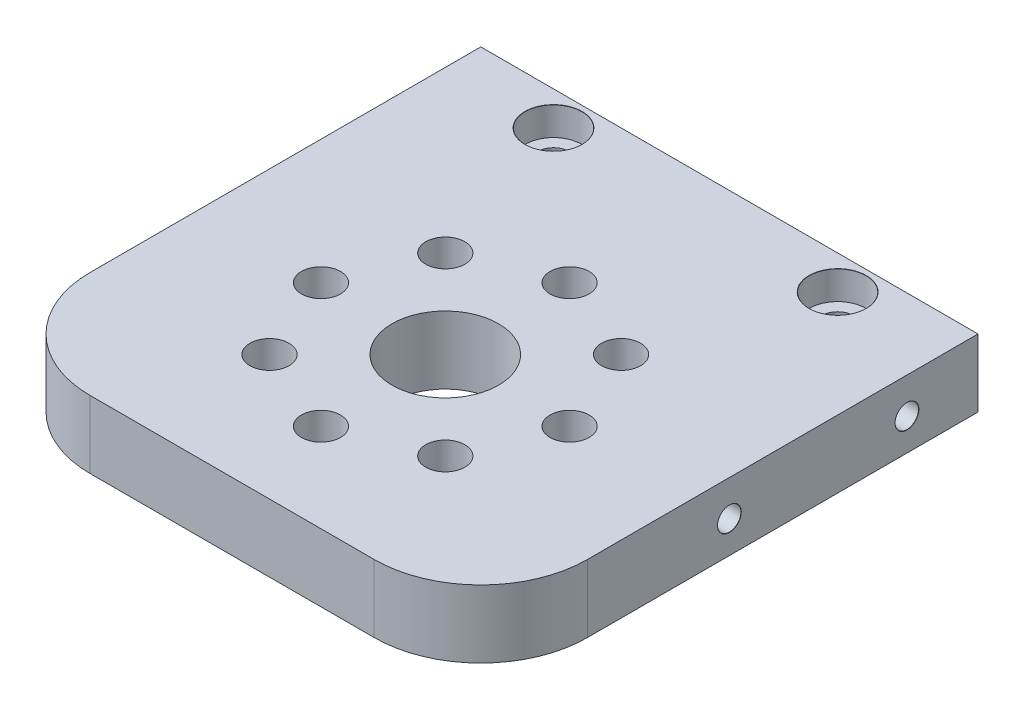
SolidWorks part; units mm, degrees
material "1060 Alloy"
ref_plane "Front Plane" through (0, 0, 0) normal (0, 0, 1) x (1, 0, 0)
ref_plane "Top Plane" through (0, 0, 0) normal (0, 1, 0) x (1, 0, 0)
ref_plane "Right Plane" through (0, 0, 0) normal (1, 0, 0) x (0, 0, -1)
sketch "Sketch1" plane through (0, 0, 0) normal (0, 1, 0) x (1, 0, 0)
  line L1 (-35, -35) -> (35, -35)
  line L2 (-35, -35) -> (-35, 35)
  line L3 (-35, 35) -> (35, 35)
  line L4 (35, -35) -> (35, 35)
  line L5 (-35, -35) -> (35, 35) construction
  line L6 (-35, 35) -> (35, -35) construction
  point P0 (0, 0)
  dimension "D1" = 70
  dimension "D2" = 70
extrude "Boss-Extrude1" add sketch "Sketch1" along normal blind 9.525
sketch "Sketch2" plane through (0, 0, 0) normal (0, -1, 0) x (1, 0, 0)
  line L1 (-35, 35) -> (35, 35) construction
  line L2 (-35, -35) -> (-35, 35) construction
  circle A0 centre (0, 5) radius 17.5 construction
  point P4 (0, 22.5)
  point P6 (12.3744, 17.3744)
  point P7 (17.5, 5)
  point P8 (12.3744, -7.3744)
  point P9 (0, -12.5)
  point P10 (-12.3744, -7.3744)
  point P11 (-17.5, 5)
  point P12 (-12.3744, 17.3744)
  point P13 (0, 5)
  dimension "D2" = 35
  dimension "D3" = 30
  dimension "D4" = 35
  dimension "D1" = 8
hole_wizard "CBORE for M5 SHCS2" positions "Sketch3" profile "Sketch4" counterbore size "M5" standard "ANSI Metric" end condition through all
sketch "Sketch3" plane through (0, 0, 0) normal (0, -1, 0) x (-1, 0, 0)
  point P0 (0, -22.5)
  point P3 (-12.3744, -17.3744)
  point P6 (-17.5, -5)
  point P9 (-12.3744, 7.3744)
  point P12 (0, 12.5)
  point P15 (12.3744, 7.3744)
  point P18 (17.5, -5)
  point P21 (12.3744, -17.3744)
sketch "Sketch4" plane through (0, 0, 22.5) normal (1, 0, 0) x (0, 0, -1)
  line L0 (0, 0) -> (0, 9.525)
  line L1 (0, 9.525) -> (2.75, 9.525)
  line L3 (2.75, 9.525) -> (2.75, 5)
  line L4 (5, 5) -> (2.75, 5)
  line L5 (5, 5) -> (5, 0.025)
  line L6 (5, 0.025) -> (5.025, 0)
  line L7 (5.025, 0) -> (0, 0)
  line L8 (-5, 0.025) -> (-5.025, 0) construction
  line L11 (0, -6.35) -> (0, 107.95) construction
  dimension "Thru Hole Dia." = 5.5
  dimension "Thru Hole Depth" = 9.525
  dimension "C'Bore Dia." = 10
  dimension "C'Bore Depth" = 5
  dimension "Near C'Sink Dia." = 10.05
  dimension "Near C'Sink Angle" = 90
sketch "Sketch5" plane through (35, 0, 0) normal (1, 0, 0) x (0, 0, -1)
  line L0 (35, 4.5) -> (-35, 4.5) construction
  line L1 (35, 9.525) -> (35, 0) construction
  line L3 (-35, 0) -> (35, 0) construction
  point P6 (25, 4.5)
  point P7 (0, 4.5)
  dimension "D1" = 10
  dimension "D2" = 25
  dimension "D3" = 4.5
hole_wizard "Tap Drill for M4x0.7 Tap1" positions "Sketch6" profile "Sketch8" hole size "M4x0.7" standard "ANSI Metric"
sketch "Sketch6" plane through (35, 0, 0) normal (1, 0, 0) x (0, 0, -1)
  point P0 (0, 4.5)
  point P3 (25, 4.5)
sketch "Sketch8" plane through (35, 4.5, 0) normal (0, 1, 0) x (0, 0, -1)
  line L0 (0, 0) -> (0, 8.9914)
  line L1 (0, 8.9914) -> (1.65, 8)
  line L2 (1.65, 8) -> (1.65, 0.025)
  line L3 (1.65, 0.025) -> (1.675, 0)
  line L5 (1.675, 0) -> (0, 0)
  line L6 (-1.65, 0.025) -> (-1.675, 0) construction
  line L10 (0, 8.9914) -> (-1.65, 8) construction
  line L11 (0, -6.35) -> (0, 107.95) construction
  dimension "Hole Dia." = 3.3
  dimension "Hole Depth" = 8
  dimension "Near C'Sink Dia." = 3.35
  dimension "Near C'Sink Angle" = 90
  dimension "Drill Angle" = 118
sketch "Sketch9" plane through (0, 0, 0) normal (0, -1, 0) x (1, 0, 0)
  circle A0 centre (0, 5) radius 7.5
  circle A1 centre (0, 5) radius 17.5 construction
  dimension "D1" = 15
extrude "Cut-Extrude1" cut sketch "Sketch9" against normal through all
sketch "Sketch10" plane through (0, 9.525, 0) normal (0, -1, 0) x (1, 0, 0)
  line L0 (35, -30.2375) -> (-35, -30.2375) construction
  line L1 (35, 35) -> (35, -35) construction
  line L2 (-35, -35) -> (-35, 35) construction
  line L3 (35, -35) -> (-35, -35) construction
  line L4 (0, -5.2388) -> (0, 5.2388) construction
  point P8 (20, -30.2375)
  point P11 (-20, -30.2375)
  dimension "D1" = 4.7625
  dimension "D2" = 15
hole_wizard "CBORE for M4 SHCS1" positions "Sketch14" profile "Sketch15" counterbore size "M4" standard "ANSI Metric" end condition through all
sketch "Sketch14" plane through (0, 9.525, 0) normal (0, 1, 0) x (1, 0, 0)
  point P0 (-20, 30.2375)
  point P3 (20, 30.2375)
sketch "Sketch15" plane through (-20, 9.525, -30.2375) normal (1, 0, 0) x (0, 0, 1)
  line L0 (0, 0) -> (0, 9.525)
  line L1 (0, 9.525) -> (2.25, 9.525)
  line L3 (2.25, 9.525) -> (2.25, 4)
  line L4 (4, 4) -> (2.25, 4)
  line L5 (4, 4) -> (4, 0.025)
  line L6 (4, 0.025) -> (4.025, 0)
  line L7 (4.025, 0) -> (0, 0)
  line L8 (-4, 0.025) -> (-4.025, 0) construction
  line L11 (0, -6.35) -> (0, 107.95) construction
  dimension "Thru Hole Dia." = 4.5
  dimension "Thru Hole Depth" = 9.525
  dimension "C'Bore Dia." = 8
  dimension "C'Bore Depth" = 4
  dimension "Near C'Sink Dia." = 8.05
  dimension "Near C'Sink Angle" = 90
mirror "Mirror1" about plane through (0, 0, 0) normal (1, 0, 0) of "Tap Drill for M4x0.7 Tap1"
fillet "Fillet1" radius 15 2 edges at (-35, 4.7625, 35) (35, 4.7625, 35)
